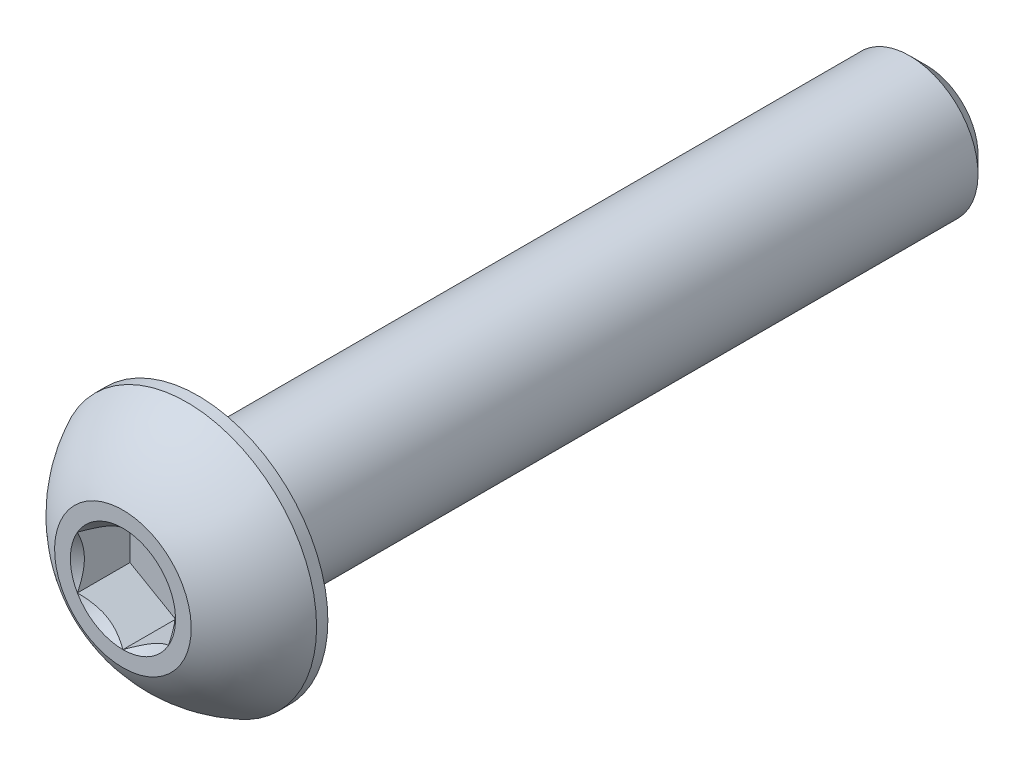
SolidWorks part; units mm, degrees
material "AISI 304"
ref_plane "Front" through (0, 0, 0) normal (0, 0, 1) x (1, 0, 0)
ref_plane "Top" through (0, 0, 0) normal (0, 1, 0) x (1, 0, 0)
ref_plane "Right" through (0, 0, 0) normal (1, 0, 0) x (0, 0, -1)
sketch "Sketch1" plane through (0, 0, 0) normal (1, 0, 0) x (0, 0, -1)
  line L2 (1.65, 1.5) -> (17.65, 1.5)
  line L3 (17.65, 1.5) -> (17.65, 0)
  line L4 (17.65, 0) -> (1.65, 0)
  line L6 (1.4025, 2.85) -> (1.65, 2.85) construction
  line L7 (17.65, 1.5) -> (17.65, -1.5) construction
  line L8 (0, 0) -> (1.65, 0) construction
  line L9 (1.65, 2.85) -> (1.65, -2.85) construction
  line L11 (1.65, 1.5) -> (1.65, 0)
  line L13 (0, 1) -> (0, -1) construction
  line L14 (0, 1) -> (0, 1.5) construction
  arc A3 (0, 1.5) -> (1.4025, 2.85) centre (2.7948, 0) cw construction
  dimension "D1" = 0.2475
revolve "Revolve1" add sketch "Sketch1" angle 360 mid plane about L4
sketch "Sketch3" plane through (0, 0, -17.65) normal (0, 0, -1) x (-1, 0, 0)
  circle A0 centre (0, 0) radius 1.5
curve "Helix/Spiral1" pitch 0.5 height 16.5 turns 33
chamfer "Chamfer1" distance 0.375 angle 45 1 edges at (0, 1.5, -17.65)
sketch "Sketch7" plane through (0, 0, 0) normal (1, 0, 0) x (0, 0, -1)
  line L6 (1.4025, 2.85) -> (1.65, 2.85) construction
  line L8 (0, 0) -> (1.65, 0) construction
  line L11 (1.65, 2.85) -> (1.65, -2.85) construction
  line L12 (1.4025, 2.85) -> (1.65, 2.85)
  line L13 (0, 0) -> (1.65, 0)
  line L14 (0, 1) -> (0, -1) construction
  line L15 (1.65, 2.85) -> (1.65, 0)
  line L16 (0, 1.5) -> (0, 0)
  arc A2 (1.4025, 2.85) -> (0, 1.5) centre (2.7948, 0) ccw construction
  arc A3 (1.4025, 2.85) -> (0, 1.5) centre (2.7948, 0) ccw
revolve "Revolve2" add sketch "Sketch7" angle 360 mid plane about L13
sketch "Sketch5" plane through (0, 0, 0) normal (0, 0, 1) x (1, 0, 0)
  line L1 (1, -0.5774) -> (1, 0.5774)
  line L2 (1, 0.5774) -> (0, 1.1547)
  line L3 (0, 1.1547) -> (-1, 0.5774)
  line L4 (-1, 0.5774) -> (-1, -0.5774)
  line L5 (-1, -0.5774) -> (0, -1.1547)
  line L6 (0, -1.1547) -> (1, -0.5774)
  circle A0 centre (0, 0) radius 1 construction
extrude "Cut-Extrude2" cut sketch "Sketch5" against normal blind 1.155
sketch "Sketch6" plane through (0, 0, 0) normal (0, 0, 1) x (1, 0, 0)
  circle A0 centre (0, 0) radius 1.1547
extrude "Cut-Extrude3" cut sketch "Sketch6" against normal blind 1.155 draft 45
sketch "Sketch2" [suppressed] plane through (0, 0, 0) normal (1, 0, 0) x (0, 0, -1)
  line L0 (17.275, 1.5) -> (17.7125, 1.5)
  line L1 (17.7125, 1.5) -> (17.525, 1.1752)
  line L2 (17.525, 1.1752) -> (17.4625, 1.1752)
  line L3 (17.4625, 1.1752) -> (17.275, 1.5)
  line L4 (17.3687, 1.3376) -> (17.6187, 1.3376) construction
  dimension "D1" = 60
  dimension "D2" = 0.0625
  dimension "D3" = 0.25
sweep "Cut-Sweep1" [suppressed] cut profiles "Sketch2" path "Helix/Spiral1"
sketch "Sketch10" [suppressed] plane through (0, 0, 0) normal (1, 0, 0) x (0, 0, -1)
  line L0 (17.65, 1.5) -> (17.65, -1.5) construction
  point P0 (16.9, -1.5)
  dimension "D1" = 0.75
ref_axis "Center Axis 1" through (0, 0, -8.1113) along (0, 0, 1)
ref_plane "Contact Plane 1" through (0, 0, -1.65) normal (0, 0, -1) x (-1, 0, 0)
ref_plane "Contact Plane 2" through (0, 0, 0) normal (0, 0, 1) x (1, 0, 0)
equation "\"D3@Helix/Spiral1\" = \"Lg@Sketch1\" + \"D4@Helix/Spiral1\""
equation "\"D2@Sketch2\" = \"D4@Helix/Spiral1\" * .125"
equation "\"D3@Sketch2\" = \"D4@Helix/Spiral1\" * .5"
equation "\"D1@Chamfer1\" = \"D4@Helix/Spiral1\" * .75"
equation "\"D1@Cut-Extrude2\" = \"Head Ht@Sketch1\" * .7"
equation "\"D1@Sketch1\" = \"Head Ht@Sketch1\" * .15"
equation "\"D1@Sketch10\" = \"D4@Helix/Spiral1\" * 1.5"
equation "\"D1@Cut-Extrude3\" = \"D1@Cut-Extrude2\""
